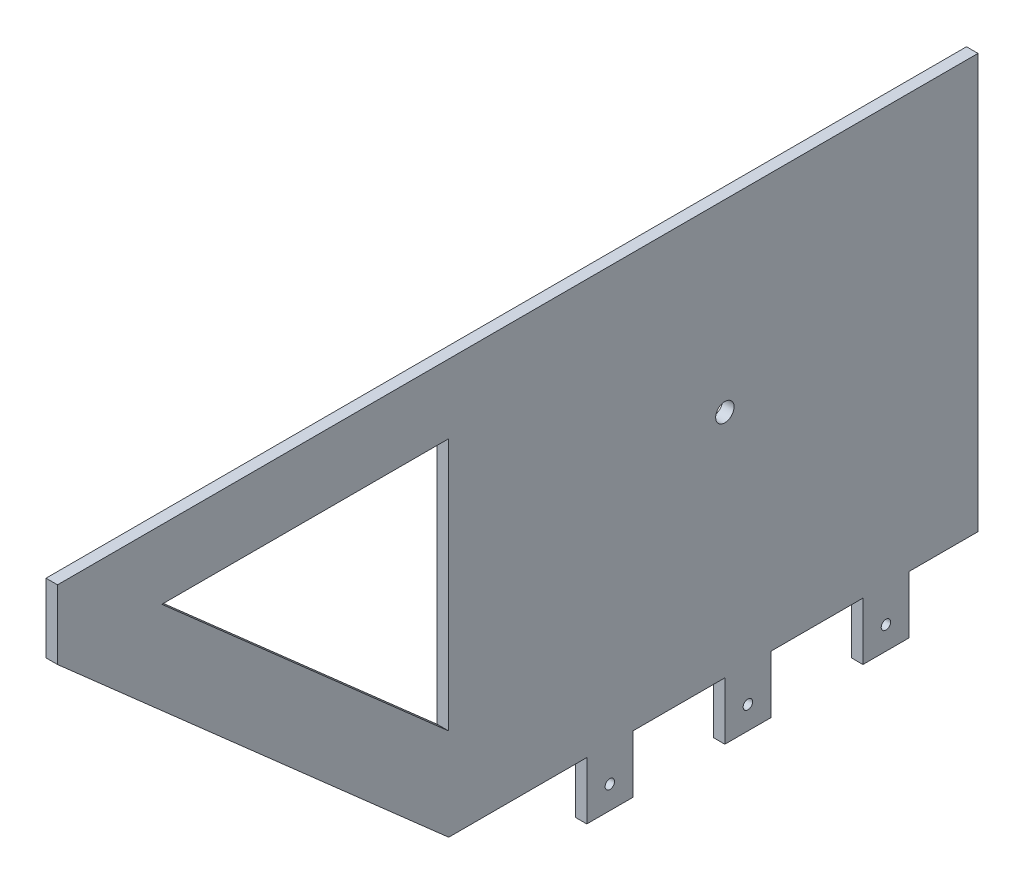
SolidWorks part; units mm, degrees
ref_plane "前基準面" through (0, 0, 0) normal (0, 0, 1) x (1, 0, 0)
ref_plane "上基準面" through (0, 0, 0) normal (0, 1, 0) x (1, 0, 0)
ref_plane "右基準面" through (0, 0, 0) normal (1, 0, 0) x (0, 0, -1)
sketch "草圖1" plane through (0, 0, 0) normal (1, 0, 0) x (0, 0, -1)
  line L1 (100, 90) -> (-100, 90)
  line L2 (100, 90) -> (100, -90)
  line L3 (100, -90) -> (-100, -90)
  line L4 (-100, 90) -> (-100, -90)
  line L5 (0, -90) -> (0, 90) construction
  line L6 (100, 0) -> (-100, 0) construction
  circle A0 centre (-10, 10) radius 4
  point P0 (0, 0)
  dimension "D3" = 8
  dimension "D1" = 200
  dimension "D2" = 180
  dimension "D4" = 100
  dimension "D5" = 90
extrude "填料-伸長1" add sketch "草圖1" along normal blind 5
sketch "草圖2" plane through (5, 0, 0) normal (1, 0, 0) x (0, 0, -1)
  line L0 (-100, -90) -> (100, -90) construction
  line L1 (-70, -90) -> (-50, -90)
  line L4 (-70, -90) -> (-70, -115)
  line L5 (-70, -115) -> (-50, -115)
  line L6 (-50, -115) -> (-50, -90)
  line L8 (-10, -90) -> (-10, -115)
  line L9 (-10, -115) -> (10, -115)
  line L10 (10, -115) -> (10, -90)
  line L12 (50, -90) -> (50, -115)
  line L13 (50, -115) -> (70, -115)
  line L14 (70, -115) -> (70, -90)
  line L17 (-100, 90) -> (-100, -90) construction
  line L18 (-70, -105) -> (70, -105) construction
  line L19 (-10, -90) -> (10, -90)
  line L20 (50, -90) -> (70, -90)
  line L21 (-70, -95) -> (70, -95) construction
  circle A0 centre (-60, -105) radius 2.05
  circle A1 centre (0, -105) radius 2.05
  circle A2 centre (60, -105) radius 2.05
  point P11 (0, -105)
  point P12 (0, 0)
  point P15 (0, -105)
  point P16 (0, 0)
  point P27 (-60, -115)
  point P30 (60, -115)
  point P32 (0, -90)
  dimension "D7" = 4.1
  dimension "D1" = 25
  dimension "D2" = 30
  dimension "D3" = 40
  dimension "D4" = 40
  dimension "D5" = 20
  dimension "D6" = 5
  dimension "D8" = 10
extrude "填料-伸長2" add sketch "草圖2" against normal blind 5
sketch "草圖3" plane through (5, 0, 0) normal (1, 0, 0) x (0, 0, -1)
  line L0 (-100, -90) -> (100, -90) construction
  line L1 (-100, 90) -> (-100, -90) construction
  line L2 (100, -90) -> (100, 90) construction
  line L4 (-100, 90) -> (-300, 90)
  line L5 (-300, 90) -> (-300, 60)
  line L6 (-300, 60) -> (-130, -90)
  line L7 (-130, -90) -> (-100, -90)
  line L8 (-100, 90) -> (-100, -90)
  line L9 (-130, 60) -> (-130, -49.9914)
  line L10 (-130, -49.9914) -> (-130, -49.9914)
  line L11 (-254.6569, 60) -> (-130, -49.9914)
  line L12 (-254.6569, 60) -> (-254.6569, 60)
  line L13 (-130, 60) -> (-254.6569, 60)
  line L14 (-100, -90) -> (-70, -90) construction
  dimension "D2" = 30
  dimension "D3" = 30
  dimension "D4" = 200
  dimension "D5" = 30
extrude "填料-伸長3" add sketch "草圖3" against normal blind 5
